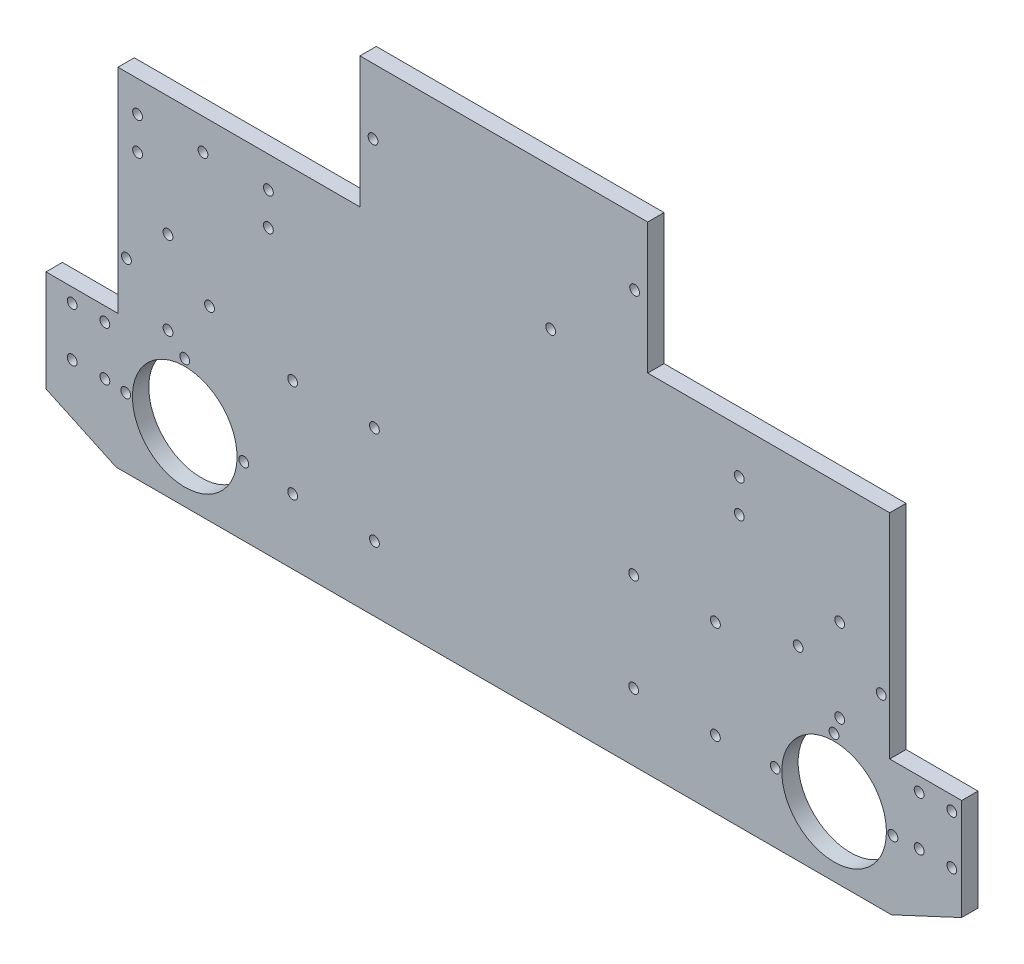
SolidWorks part; units mm, degrees
ref_plane "Front" through (0, 0, 0) normal (0, 0, 1) x (1, 0, 0)
ref_plane "Top" through (0, 0, 0) normal (0, 1, 0) x (1, 0, 0)
ref_plane "Right" through (0, 0, 0) normal (1, 0, 0) x (0, 0, -1)
sketch "Esquisse1" plane through (0, 0, 0) normal (0, 0, 1) x (1, 0, 0)
  line L2 (0, 0) -> (0, 65.2)
  line L3 (74, 138.2) -> (162, 138.2)
  line L4 (236, 0) -> (236, 65.2)
  line L7 (0, 65.2) -> (74, 65.2)
  line L8 (74, 138.2) -> (74, 65.2)
  line L9 (0, 0) -> (-22, 0)
  line L10 (0, 0) -> (0, -37)
  line L11 (236, 65.2) -> (162, 65.2)
  line L12 (162, 138.2) -> (162, 65.2)
  line L14 (0, 0) -> (0, 34)
  line L18 (236, 0) -> (236, 34)
  line L22 (0, 0) -> (0, -37)
  line L23 (0, -37) -> (236, -37)
  line L24 (236, 0) -> (236, -37)
  line L25 (0, -37) -> (-22, -37)
  line L26 (-22, 0) -> (-22, -37)
  line L27 (236, 0) -> (258, 0)
  line L28 (236, 0) -> (236, -37)
  line L29 (236, -37) -> (258, -37)
  line L30 (258, 0) -> (258, -37)
  dimension "D2" = 175.2
  dimension "D3" = 88
  dimension "D4" = 65.2
  dimension "D5" = 65.2
  dimension "D6" = 74
  dimension "D8" = 34
  dimension "D9" = 34
  dimension "D11" = 37
  dimension "D16" = 74
  dimension "D18" = 22
  dimension "D19" = 22
extrude "Boss.-Extru.2" add sketch "Esquisse1" along normal blind 5 contours L22 L23 L24 L4 L11 L12 L3 L8 L7 L2 | L30 L27 L24 L29 | L9 L26 L25 L10 region at (-11, -18.5, 0) region at (118, 32.5245, 0) region at (247, -18.5, 0)
sketch "Esquisse2" plane through (0, 0, 5) normal (0, 0, 1) x (1, 0, 0)
  circle A17 centre (26, 55.7) radius 1.5
  circle A21 centre (46, 55.7) radius 1.5
  circle A313 centre (6, 55.7) radius 1.5
  circle A315 centre (6, 45.7) radius 1.5
  circle A321 centre (-4, -4.3) radius 1.5
  circle A323 centre (-14, -4.3) radius 1.5
  circle A393 centre (-4, -19.3) radius 1.5
  circle A395 centre (-14, -19.3) radius 1.5
extrude "Enlèv. mat.-Extru.1" cut sketch "Esquisse2" against normal blind 14
sketch "Esquisse3" plane through (0, 0, 5) normal (0, 0, 1) x (1, 0, 0)
  circle A155 centre (132.3312, 62.0023) radius 1.5
extrude "Enlèv. mat.-Extru.2" cut sketch "Esquisse3" against normal blind 32
sketch "Esquisse4" plane through (0, 0, 0) normal (0, 0, -1) x (-1, 0, 0)
  circle A0 centre (-190, 51.7) radius 1.5
  circle A1 centre (-190, 41.7) radius 1.5
  dimension "D1" = 3
  dimension "D2" = 3
extrude "Enlèv. mat.-Extru.3" cut sketch "Esquisse4" against normal through all
sketch "Esquisse5" plane through (0, 0, 5) normal (0, 0, 1) x (1, 0, 0)
  circle A0 centre (46, 45.7) radius 1.5006
  dimension "D1" = 3.0012
extrude "Enlèv. mat.-Extru.4" cut sketch "Esquisse5" against normal through all
sketch "Esquisse6" plane through (0, 0, 5) normal (0, 0, 1) x (1, 0, 0)
  circle A0 centre (245, -4.3) radius 1.5
  circle A1 centre (255, -4.3) radius 1.5
  circle A2 centre (255, -19.3) radius 1.5
  circle A3 centre (245, -19.3) radius 1.5
  dimension "D1" = 3
  dimension "D2" = 3
  dimension "D3" = 3
  dimension "D4" = 3
extrude "Enlèv. mat.-Extru.5" cut sketch "Esquisse6" against normal through all
sketch "Esquisse7" plane through (0, 0, 0) normal (0, 0, -1) x (-1, 0, 0)
  circle A0 centre (-15.3, 28.6) radius 1.5
  circle A1 centre (-2.6, 15.9) radius 1.5
  circle A2 centre (-15.3, 3.2) radius 1.5
  circle A3 centre (-28, 15.9) radius 1.5
  circle A4 centre (-208, 15.9) radius 1.5
  circle A5 centre (-220.7, 3.2) radius 1.5
  circle A6 centre (-233.4, 15.9) radius 1.5
  circle A7 centre (-220.7, 28.6) radius 1.5
  dimension "D1" = 3
  dimension "D2" = 3
  dimension "D3" = 3
  dimension "D4" = 3
  dimension "D5" = 3
  dimension "D6" = 3
  dimension "D7" = 3
  dimension "D8" = 3
extrude "Enlèv. mat.-Extru.6" cut sketch "Esquisse7" against normal through all
sketch "Esquisse8" plane through (0, 0, 5) normal (0, 0, 1) x (1, 0, 0)
  line L0 (162, 138.2) -> (162, 65.2) construction
  line L1 (74, 138.2) -> (162, 138.2)
  line L2 (74, 138.2) -> (74, 105.2)
  line L3 (74, 105.2) -> (162, 105.2)
  line L4 (162, 138.2) -> (162, 105.2)
  dimension "D1" = 33
extrude "Enlèv. mat.-Extru.7" cut sketch "Esquisse8" against normal through all
sketch "Esquisse9" plane through (0, 0, 5) normal (0, 0, 1) x (1, 0, 0)
  circle A0 centre (182.7, -20.4) radius 1.5
  circle A1 centre (157.7, -20.4) radius 1.5
  circle A2 centre (157.7, 9.6) radius 1.5
  circle A3 centre (182.7, 9.6) radius 1.5074
  circle A4 centre (78.4242, -21.0951) radius 1.5
  circle A5 centre (53.4242, -21.0951) radius 1.5
  circle A6 centre (78.4242, 8.9049) radius 1.5
  circle A7 centre (53.4242, 8.9049) radius 1.5
  dimension "D1" = 3
  dimension "D2" = 3
  dimension "D3" = 3
  dimension "D4" = 3
  dimension "D5" = 3
  dimension "D6" = 3
  dimension "D7" = 3
  dimension "D8" = 3.0147
extrude "Enlèv. mat.-Extru.8" cut sketch "Esquisse9" against normal through all
sketch "Esquisse10" plane through (0, 0, 5) normal (0, 0, 1) x (1, 0, 0)
  line L1 (-22, -37) -> (258, -37)
  line L2 (-22, -37) -> (-22, -41)
  line L3 (-22, -41) -> (258, -41)
  line L4 (258, -37) -> (258, -41)
  dimension "D1" = 4
extrude "Boss.-Extru.3" add sketch "Esquisse10" against normal blind 5
sketch "Esquisse12" plane through (0, 0, 5) normal (0, 0, 1) x (1, 0, 0)
  circle A0 centre (20.4242, -19.8) radius 16
  circle A1 centre (219, -19.8) radius 16
  dimension "D1" = 32
  dimension "D2" = 32
extrude "Enlèv. mat.-Extru.10" cut sketch "Esquisse12" against normal through all
sketch "Esquisse13" plane through (0, 0, 5) normal (0, 0, 1) x (1, 0, 0)
  circle A0 centre (2.3835, -19.8) radius 1.5
  circle A1 centre (20.4242, -1.7412) radius 1.5
  circle A2 centre (38.4788, -20.0401) radius 1.5
  circle A4 centre (218.9653, -1.7412) radius 1.5
  circle A5 centre (236.9863, -19.8) radius 1.5
  circle A6 centre (200.9946, -19.8) radius 1.5
  dimension "D1" = 3
  dimension "D2" = 3
  dimension "D3" = 3
  dimension "D6" = 3
  dimension "D7" = 3
  dimension "D8" = 3
extrude "Enlèv. mat.-Extru.11" cut sketch "Esquisse13" against normal through all
chamfer "Chanfrein1" distance 10 angle 65 1 edges at (-22, -41, 2.5) first distance on face at (-22, -20.5, 2.5)
chamfer "Chanfrein2" distance 10 angle 65 1 edges at (258, -41, 2.5) first distance on face at (258, -20.5, 2.5)
sketch "Esquisse14" plane through (0, 0, 0) normal (0, 0, -1) x (-1, 0, 0)
  circle A0 centre (-158, 85.2) radius 1.5
  circle A1 centre (-78, 85.2) radius 1.5
  dimension "D1" = 3
  dimension "D2" = 3
extrude "Enlèv. mat.-Extru.12" cut sketch "Esquisse14" against normal through all
